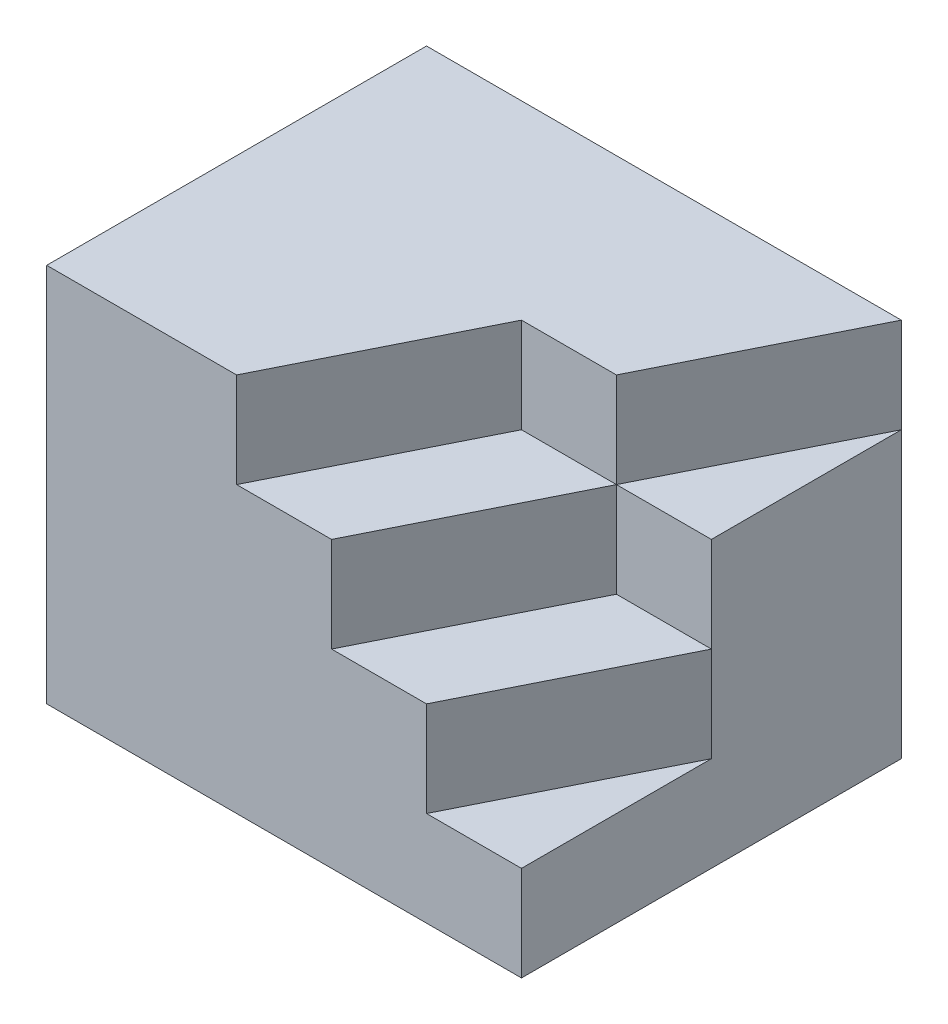
SolidWorks part; units mm, degrees
ref_plane "Front Plane" through (0, 0, 0) normal (0, 0, 1) x (1, 0, 0)
ref_plane "Top Plane" through (0, 0, 0) normal (0, 1, 0) x (1, 0, 0)
ref_plane "Right Plane" through (0, 0, 0) normal (1, 0, 0) x (0, 0, -1)
sketch "Sketch1" plane through (0, 0, 0) normal (0, 1, 0) x (1, 0, 0)
  line L0 (5, -20) -> (25, 20)
  line L1 (25, -20) -> (-25, -20)
  line L2 (25, -20) -> (25, 20)
  line L3 (25, 20) -> (-25, 20)
  line L4 (-25, -20) -> (-25, 20)
  line L5 (25, -20) -> (-25, 20) construction
  line L6 (25, 20) -> (-25, -20) construction
  line L7 (15, -20) -> (25, 0)
  line L8 (25, 0) -> (5, 0)
  line L9 (5, 0) -> (-5, -20)
  point P0 (0, 0)
  point P6 (15, -20)
  point P7 (5, -20)
  point P8 (-5, -20)
  point P10 (25, 0)
  dimension "D1" = 40
  dimension "D2" = 50
  dimension "D3" = 10
  dimension "D4" = 10
  dimension "D5" = 10
  dimension "D6" = 20
extrude "Boss-Extrude1" add sketch "Sketch1" along normal blind 40 contours L9 L8 L0 L3 L4 L1 region at (-5.9524, 0, -3.3333)
extrude "Boss-Extrude2" add sketch "Sketch1<3>" along normal blind 30 contours L8 L9 L1 L0 | L8 L2 L0 region at (5, 0, 10) region at (21.6667, 0, -6.6667)
sketch "Sketch1<3>" plane through (0, 0, 0) normal (0, 1, 0) x (1, 0, 0) same geometry as "Sketch1"
extrude "Boss-Extrude3" add sketch "Sketch1<4>" along normal blind 20 contours L7 L8 L0 L1 region at (15, 0, 10)
sketch "Sketch1<4>" plane through (0, 0, 0) normal (0, 1, 0) x (1, 0, 0) same geometry as "Sketch1"
extrude "Boss-Extrude4" add sketch "Sketch1<5>" along normal blind 10 contours L7 L1 L2 region at (21.6667, 0, 13.3333)
sketch "Sketch1<5>" plane through (0, 0, 0) normal (0, 1, 0) x (1, 0, 0) same geometry as "Sketch1"
